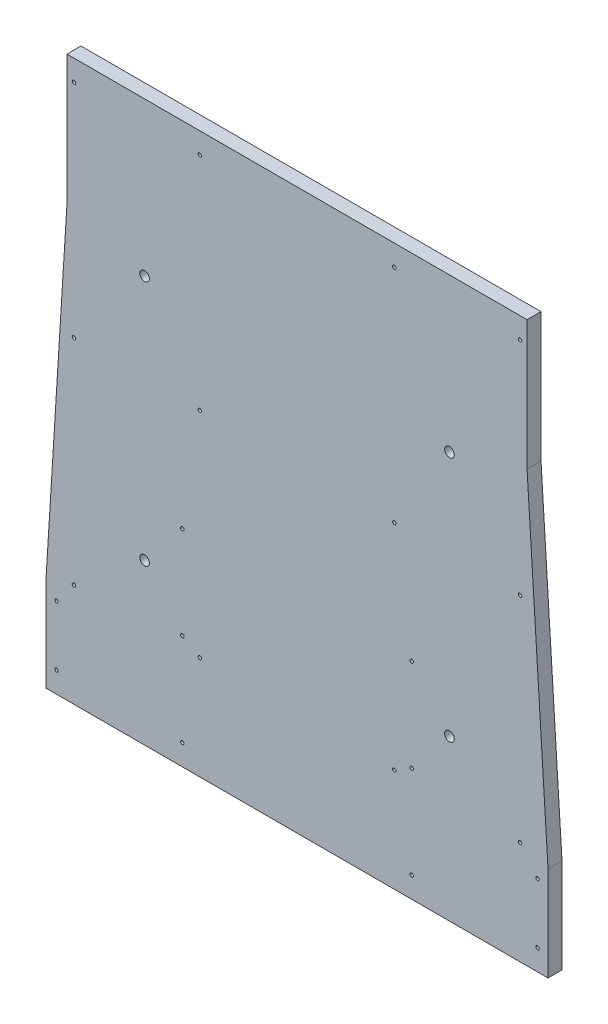
SolidWorks part; units mm, degrees
material "MDF"
ref_plane "Front Plane" through (0, 0, 0) normal (0, 0, 1) x (1, 0, 0)
ref_plane "Top Plane" through (0, 0, 0) normal (0, 1, 0) x (1, 0, 0)
ref_plane "Right Plane" through (0, 0, 0) normal (1, 0, 0) x (0, 0, -1)
sketch "Sketch1" plane through (0, 0, 0) normal (0, 0, 1) x (1, 0, 0)
  line L0 (0, -4273.1683) -> (0, -5592.0408) construction
  line L1 (209.0395, -5469.1795) -> (-209.0395, -5469.1795)
  line L2 (209.0395, -5469.1795) -> (209.0395, -5053.2545)
  line L3 (209.0395, -5053.2545) -> (-209.0395, -5053.2545)
  line L4 (0, -5469.1795) -> (0, -5053.2545) construction
  line L5 (-209.0395, -5469.1795) -> (-209.0395, -5053.2545)
  dimension "D1" = 209.0395
  dimension "D2" = 120.65
  dimension "D3" = 415.925
extrude "Boss-Extrude1" add sketch "Sketch1" along normal blind 12.7
sketch "Sketch2" plane through (0, 0, 0) normal (0, 0, -1) x (-1, 0, 0)
  line L1 (-209.0395, -5469.1795) -> (209.0395, -5469.1795)
  line L2 (-209.0395, -5469.1795) -> (-209.0395, -5548.8695)
  line L3 (-209.0395, -5548.8695) -> (209.0395, -5548.8695)
  line L4 (209.0395, -5469.1795) -> (209.0395, -5548.8695)
  line L8 (209.0395, -5053.2545) -> (209.0395, -5469.1795) construction
  dimension "D1" = 79.69
extrude "Boss-Extrude2" add sketch "Sketch2" against normal through all
sketch "Sketch3" plane through (0, 0, 0) normal (0, 0, -1) x (-1, 0, 0)
  line L1 (209.0395, -5024.8784) -> (-209.0395, -5024.8784)
  line L2 (209.0395, -5024.8784) -> (209.0395, -5053.2545)
  line L3 (209.0395, -5053.2545) -> (-209.0395, -5053.2545)
  line L4 (-209.0395, -5024.8784) -> (-209.0395, -5053.2545)
extrude "Boss-Extrude3" add sketch "Sketch3" against normal through all
sketch "Sketch4" plane through (0, 0, 0) normal (0, 0, -1) x (-1, 0, 0)
  line L0 (209.0388, -5447.3528) -> (228.0888, -5447.3528)
  line L1 (228.0888, -5447.3528) -> (228.0888, -5548.8695)
  line L2 (-209.0395, -5548.8695) -> (209.0395, -5548.8695) construction
  line L3 (228.0888, -5548.8695) -> (209.0395, -5548.8695)
  line L4 (209.0395, -5548.8695) -> (209.0388, -5447.3528)
  line L5 (0, -5562.8703) -> (0, -5024.8784) construction
  line L6 (209.0395, -5024.8784) -> (-209.0395, -5024.8784) construction
  line L7 (-209.0395, -5548.8695) -> (-209.0388, -5447.3528)
  line L8 (-228.0888, -5548.8695) -> (-209.0395, -5548.8695)
  line L9 (-228.0888, -5447.3528) -> (-228.0888, -5548.8695)
  line L10 (-209.0388, -5447.3528) -> (-228.0888, -5447.3528)
extrude "Boss-Extrude4" add sketch "Sketch4" against normal through all
chamfer "Chamfer1" distance 19.05 distance2 304.8 2 edges at (-209.0395, -5447.3528, 6.35) (209.0395, -5447.3528, 6.35) first distance on face at (-218.5641, -5447.3528, 6.35) first distance on face at (218.5641, -5447.3528, 6.35)
sketch "Sketch5" plane through (228.0888, 0, 0) normal (1, 0, 0) x (0, 0, -1)
  line L0 (0, -5447.3417) -> (0, -5548.8695) construction
  line L1 (-12.7, -5548.8695) -> (0, -5548.8695)
  line L2 (-12.7, -5548.8695) -> (-12.7, -5533.4155)
  line L3 (-12.7, -5533.4155) -> (0, -5533.4155)
  line L4 (0, -5548.8695) -> (0, -5533.4155)
extrude "Cut-Extrude1" cut sketch "Sketch5" against normal through all
hole_wizard "5/16 Clearance Hole1" positions "Sketch6" profile "Sketch7" hole size "5/16" standard "ANSI Inch" end condition through all
sketch "Sketch6" plane through (0, 0, 0) normal (0, 0, -1) x (-1, 0, 0)
  circle A2 centre (-138.551, -5164.3168) radius 5.1587 construction
  circle A3 centre (138.551, -5164.3168) radius 5.1587 construction
  point P0 (138.551, -5387.9638)
  point P3 (-138.551, -5387.9638)
  point P6 (-138.551, -5164.3168)
  point P12 (138.551, -5164.3168)
sketch "Sketch7" plane through (-138.551, -5387.9638, 0) normal (1, 0, 0) x (0, 1, 0)
  line L0 (0, 0) -> (0, 12.7)
  line L1 (0, 12.7) -> (4.365, 12.7)
  line L2 (4.365, 12.7) -> (4.365, 0)
  line L5 (4.365, 0) -> (0, 0)
  line L11 (0, -6.35) -> (0, 107.95) construction
  dimension "Thru Hole Dia." = 8.73
  dimension "Thru Hole Depth" = 12.7
hole_wizard "Hole1" positions "Sketch8" profile "Sketch9" legacy
sketch "Sketch8" plane through (0, -5562.8703, -19.05) normal (0, 0, -1) x (-1, 0, 0)
  line L0 (218.5638, 29.4548) -> (218.5638, 115.5175) construction
  line L4 (202.6895, 537.9919) -> (202.6895, 97.9067) construction
  line L9 (88.3895, 537.9919) -> (88.3895, 97.9067) construction
  line L13 (104.2638, 29.4548) -> (104.2638, 235.8996) construction
  line L16 (0, 537.9919) -> (0, 29.4548) construction
  point P0 (218.5638, 102.8175)
  point P2 (218.5638, 48.5048)
  point P33 (202.6895, 123.3067)
  point P35 (202.6895, 317.9493)
  point P37 (202.6895, 518.9419)
  point P51 (88.3895, 518.9419)
  point P53 (88.3895, 317.9493)
  point P55 (88.3895, 123.3067)
  point P69 (104.2638, 216.8496)
  point P71 (104.2638, 132.6772)
  point P73 (104.2638, 48.5048)
  point P83 (-104.2638, 48.5048)
  point P84 (-104.2638, 132.6772)
  point P85 (-104.2638, 216.8496)
  point P86 (-88.3895, 123.3067)
  point P87 (-88.3895, 317.9493)
  point P88 (-88.3895, 518.9419)
  point P89 (-202.6895, 518.9419)
  point P90 (-202.6895, 317.9493)
  point P91 (-202.6895, 123.3067)
  point P92 (-218.5638, 48.5048)
  point P93 (-218.5638, 102.8175)
sketch "Sketch9" plane through (-218.5638, -5460.0528, -19.05) normal (1, 0, 0) x (0, 1, 0)
  line L0 (0, 0) -> (0, 51.7539)
  line L1 (0, 51.7539) -> (1.5875, 50.8)
  line L2 (1.5875, 50.8) -> (1.5875, 4.0177)
  line L3 (1.5875, 4.0177) -> (5.08, 0)
  line L4 (5.08, 0) -> (0, 0)
  line L5 (0, -14.3089) -> (0, 102.4216) construction
  line L6 (0, 51.7539) -> (-1.5875, 50.8) construction
  line L7 (-1.5875, 4.0177) -> (-5.08, 0) construction
  dimension "Diameter" = 3.175
  dimension "Depth" = 50.8
  dimension "C-Sink Diameter" = 10.16
  dimension "C-Sink Angle" = 82
  dimension "Drill Angle" = 118
